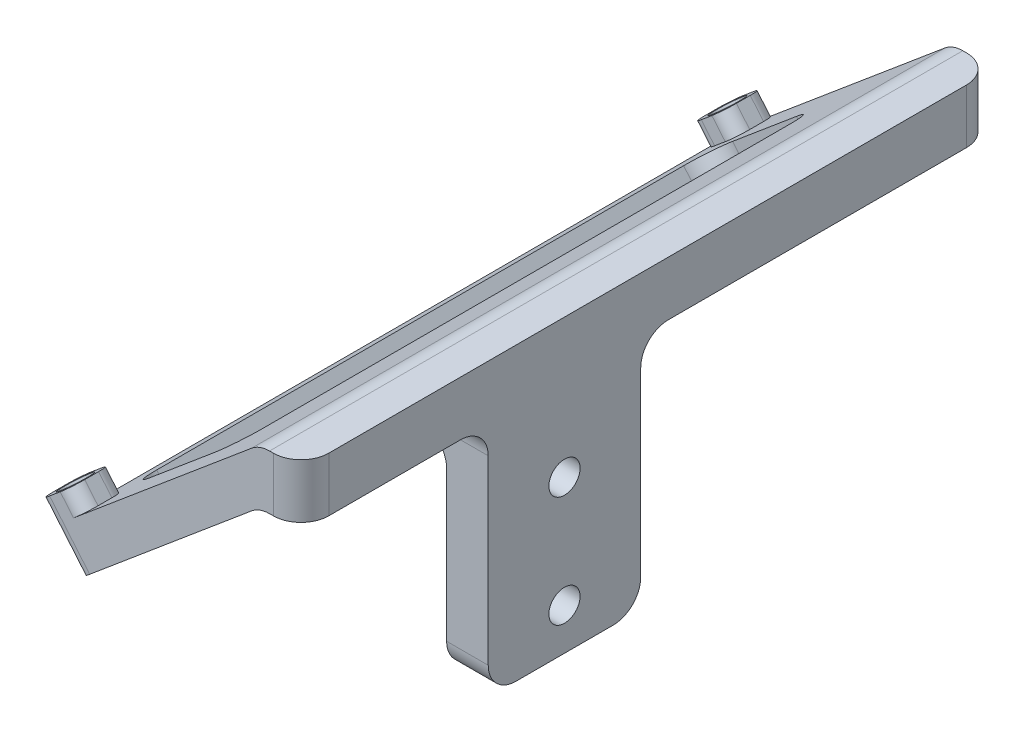
SolidWorks part; units mm, degrees
ref_plane "Front" through (0, 0, 0) normal (0, 0, 1) x (1, 0, 0)
ref_plane "Top" through (0, 0, 0) normal (0, 1, 0) x (1, 0, 0)
ref_plane "Right" through (0, 0, 0) normal (1, 0, 0) x (0, 0, -1)
sketch "Esquisse1" plane through (0, 0, 0) normal (0, 0, 1) x (1, 0, 0)
  line L0 (0, 0) -> (0, 34.1676)
  line L1 (0, 34.1676) -> (-26.019, 12.335)
  line L2 (-26.019, 12.335) -> (-29.8757, 16.9313)
  line L3 (-29.8757, 16.9313) -> (0, 42)
  line L4 (0, 42) -> (6, 42)
  line L5 (6, 42) -> (6, 0)
  line L6 (6, 0) -> (0, 0)
  line L7 (0, 34.1676) -> (0, 42) construction
  dimension "D1" = 6
  dimension "D2" = 6
  dimension "D3" = 50
  dimension "D4" = 42
  dimension "D5" = 39
extrude "Boss.-Extru.1" add sketch "Esquisse1" along normal blind 100
sketch "Esquisse2" plane through (-20.681, 24.6466, 0) normal (-0.6428, 0.766, 0) x (0.766, 0.6428, 0)
  line L0 (-12.0029, -50) -> (26.9971, -50) construction
  line L1 (-12.0029, -100) -> (-6.0029, -100)
  line L2 (-12.0029, -100) -> (-12.0029, -94)
  line L3 (-12.0029, -94) -> (-6.0029, -94)
  line L4 (-6.0029, -100) -> (-6.0029, -94)
  line L5 (-12.0029, -100) -> (-12.0029, 0) construction
  line L6 (26.9971, -100) -> (26.9971, 0) construction
  line L7 (-6.0029, 0) -> (-6.0029, -6)
  line L8 (-12.0029, -6) -> (-6.0029, -6)
  line L9 (-12.0029, 0) -> (-12.0029, -6)
  line L10 (-12.0029, 0) -> (-6.0029, 0)
  dimension "D1" = 6
  dimension "D2" = 6
extrude "Boss.-Extru.2" add sketch "Esquisse2" along normal blind 3
sketch "Esquisse3" plane through (-22.6093, 26.9447, 0) normal (-0.6428, 0.766, 0) x (0.766, 0.6428, 0)
  line L0 (-12.0029, -100) -> (-6.0029, -100) construction
  line L1 (-12.0029, -94) -> (-12.0029, -100) construction
  line L2 (-12.0029, -50) -> (26.9971, -50) construction
  line L3 (-12.0029, -94) -> (-12.0029, -6) construction
  line L4 (26.9971, -100) -> (26.9971, 0) construction
  circle A0 centre (-9.0029, -97) radius 2.25
  circle A1 centre (-9.0029, -3) radius 2.25
  point P4 (-9.0029, -100)
  dimension "D2" = 3
  dimension "D3" = 4.5
  dimension "D1" = 3
extrude "Enlèv. mat.-Extru.1" cut sketch "Esquisse3" against normal blind 5
sketch "Esquisse4" plane through (-19.3954, 23.1145, 0) normal (-0.6428, 0.766, 0) x (0.766, 0.6428, 0)
  circle A0 centre (-9.0029, -97) radius 1.75
  circle A1 centre (-9.0029, -3) radius 1.75
  dimension "D1" = 3.5
extrude "Enlèv. mat.-Extru.2" cut sketch "Esquisse4" against normal through all both and the other way through all
fillet "Congé1" radius 2 8 edges at (-28.9116, 15.7822, 0) (-26.2436, 21.9371, 0) (-26.2436, 21.9371, 6) (-30.8399, 18.0803, 6) (-30.8399, 18.0803, 94) (-26.2436, 21.9371, 94) (-26.2436, 21.9371, 100) (-28.9116, 15.7822, 100)
sketch "Esquisse5" plane through (6, 0, 0) normal (1, 0, 0) x (0, 0, -1)
  line L0 (-100, 34.1676) -> (0, 34.1676) construction
  line L1 (-100, 0) -> (-73, 0)
  line L2 (-100, 0) -> (-100, 34.1676)
  line L3 (-100, 34.1676) -> (-73, 34.1676)
  line L4 (-73, 0) -> (-73, 34.1676)
  line L6 (0, 0) -> (-51, 0)
  line L7 (0, 0) -> (0, 34.1676)
  line L8 (0, 34.1676) -> (-51, 34.1676)
  line L9 (-51, 0) -> (-51, 34.1676)
  dimension "D1" = 27
  dimension "D2" = 51
extrude "Enlèv. mat.-Extru.3" cut sketch "Esquisse5" against normal up to vertex (6 mm away) up to point (0, 34.1676, 100)
fillet "Congé2" radius 4 1 edges at (0, 34.1676, 62) tangent propagation no
sketch "Esquisse6" plane through (-20.681, 24.6466, 0) normal (-0.6428, 0.766, 0) x (0.766, 0.6428, 0)
  line L0 (-12.0029, -96) -> (-12.0029, -4) construction
  line L1 (-8.0029, -8) -> (11.9971, -8)
  line L2 (-8.0029, -8) -> (-8.0029, -92)
  line L3 (-8.0029, -92) -> (11.9971, -92)
  line L4 (11.9971, -8) -> (11.9971, -92)
  line L8 (-8.0029, -50) -> (-12.0029, -50) construction
  line L9 (-8.0029, -94) -> (-10.0029, -94) construction
  point P11 (-9.0029, -94)
  dimension "D1" = 4
  dimension "D2" = 20
  dimension "D3" = 2
extrude "Enlèv. mat.-Extru.5" cut sketch "Esquisse6" against normal up to vertex (6 mm away) up to point (-24.4869, 13.6206, 0)
fillet "Congé3" radius 4 13 edges at (0, 34.1676, 86.5) (0, 34.1676, 25.5) (0, 42, 50) (6, 38.0838, 0) (6, 38.0838, 100) (3, 34.1676, 51) (3, 34.1676, 73) (-9.5623, 30.0601, 92) (-24.8832, 17.2043, 92) (-24.8832, 17.2043, 8) (-9.5623, 30.0601, 8) (3, 0, 51) (3, 0, 73)
sketch "Esquisse7" plane through (6, 0, 0) normal (1, 0, 0) x (0, 0, -1)
  line L0 (-62, 0) -> (-62, 22) construction
  line L1 (-69, 0) -> (-55, 0) construction
  circle A0 centre (-62, 22) radius 2.25
  circle A1 centre (-62, 6) radius 2.25
  dimension "D1" = 16
  dimension "D2" = 4.5
  dimension "D3" = 6
extrude "Enlèv. mat.-Extru.6" cut sketch "Esquisse7" against normal up to vertex (6 mm away) up to point (0, 0, 55)
